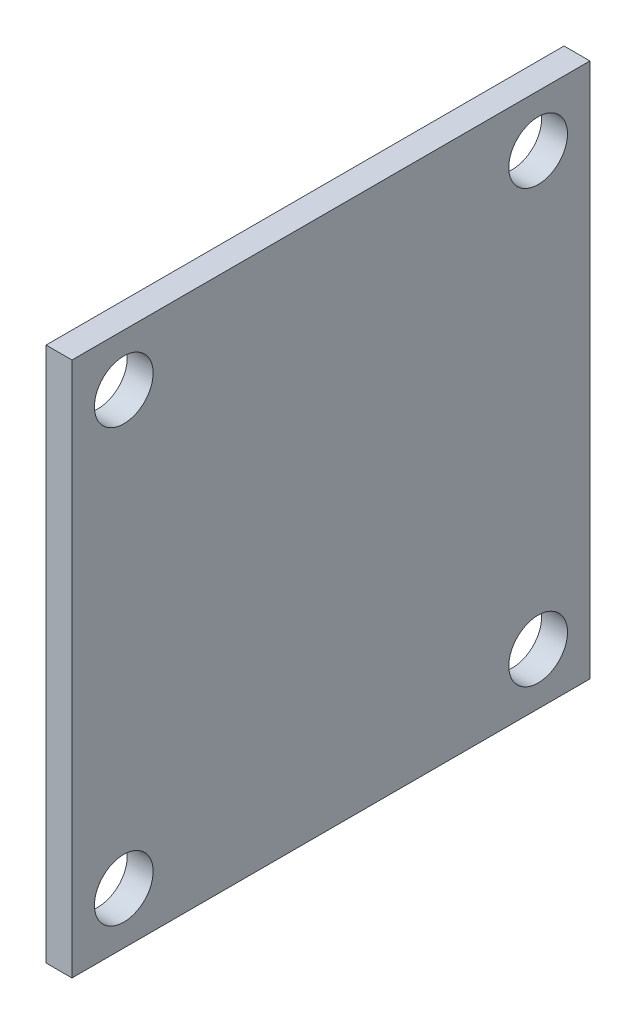
SolidWorks part; units mm, degrees
material "304单面拉丝"
ref_plane "前视" through (0, 0, 0) normal (0, 0, 1) x (1, 0, 0)
ref_plane "上视" through (0, 0, 0) normal (0, 1, 0) x (1, 0, 0)
ref_plane "右视" through (0, 0, 0) normal (1, 0, 0) x (0, 0, -1)
sketch "草图1" plane through (0, 0, 0) normal (1, 0, 0) x (0, 0, -1)
  line L1 (-15, -15.5) -> (15, -15.5)
  line L2 (-15, -15.5) -> (-15, 15.5)
  line L3 (-15, 15.5) -> (15, 15.5)
  line L4 (15, -15.5) -> (15, 15.5)
  line L5 (-15, -15.5) -> (15, 15.5) construction
  line L6 (-15, 15.5) -> (15, -15.5) construction
  point P0 (0, 0)
  dimension "D1" = 30
  dimension "D2" = 31
sheet metal parameters "钣金1" thickness 1.5 parameters "D1"=1, "厚度"=1.5
base flange "基体-法兰1" sketch "草图1" thickness 1.5 reverse thickness direction no parameters "D1"=1
hole_wizard "M3 间隙孔1" positions "草图5" profile "草图4" hole size "M3" standard "Gb"
sketch "草图5" plane through (0, 0, 0) normal (1, 0, 0) x (0, 0, -1)
  line L0 (0, 15.5) -> (0, 0) construction
  line L1 (15, 15.5) -> (-15, 15.5) construction
  line L2 (0, 0) -> (-15, 0) construction
  line L3 (-15, 15.5) -> (-15, -15.5) construction
  point P0 (-12, 12.5)
  point P13 (12, 12.5)
  point P14 (12, -12.5)
  point P15 (-12, -12.5)
  dimension "D1" = 24
  dimension "D2" = 25
sketch "草图4" plane through (0, 12.5, 12) normal (0, 1, 0) x (0, 0, -1)
  line L0 (0, 0) -> (0, 21.0215)
  line L1 (0, 21.0215) -> (1.7, 20)
  line L2 (1.7, 20) -> (1.7, 0)
  line L5 (1.7, 0) -> (0, 0)
  line L10 (0, 21.0215) -> (-1.7, 20) construction
  line L11 (0, -6.35) -> (0, 107.95) construction
  dimension "孔直径" = 3.4
  dimension "孔深度" = 20
  dimension "导头角度" = 118
flat pattern "平板型式1" [suppressed]
sketch "折弯-线1" plane through (0, 0, 0) normal (0, 1, 0) x (1, 0, 0)
sketch3d "边界框1" [suppressed]
  line L0 (-14, -13, 0) -> (14, -13, 0) construction
  line L1 (-14, 13, 0) -> (14, 13, 0) construction
  line L2 (-14, -13, 0) -> (-14, 13, 0) construction
  line L3 (14, -13, 0) -> (14, 13, 0) construction
